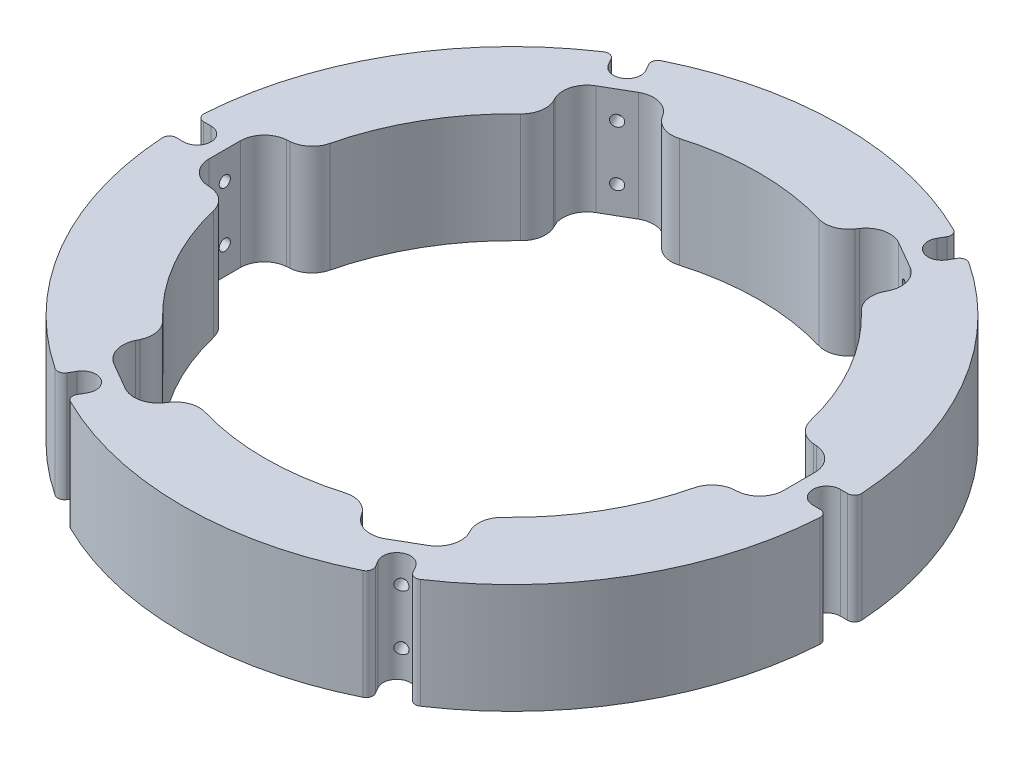
SolidWorks part; units mm, degrees
material "6061-T6 (SS)"
ref_plane "Front Plane" through (0, 0, 0) normal (0, 0, 1) x (1, 0, 0)
ref_plane "Top Plane" through (0, 0, 0) normal (0, 1, 0) x (1, 0, 0)
ref_plane "Right Plane" through (0, 0, 0) normal (1, 0, 0) x (0, 0, -1)
sketch "Sketch1" plane through (0, 0, 0) normal (0, 1, 0) x (1, 0, 0)
  circle A0 centre (0, 0) radius 76.2
  circle A1 centre (0, 0) radius 57.15
  dimension "D1" = 152.4
  dimension "D2" = 19.05
extrude "Boss-Extrude1" add sketch "Sketch1" against normal blind 12.7
sketch "Sketch3" plane through (0, -12.7, 0) normal (0, -1, 0) x (-1, 0, 0)
  line L0 (-76.1338, 3.175) -> (-72.771, 3.175)
  line L1 (-76.1338, -3.175) -> (-72.771, -3.175)
  circle A0 centre (0, 0) radius 76.2 construction
  arc A1 (-72.771, 3.175) -> (-72.771, -3.175) centre (-72.771, 0) cw
  arc A2 (-76.1338, -3.175) -> (-76.1338, 3.175) centre (0, 0) cw
  point P9 (-69.596, 0)
  point P13 (-76.2, 0)
  dimension "D1" = 6.35
  dimension "D2" = 6.604
extrude "Cut-Extrude1" cut sketch "Sketch3" against normal blind 12.7
sketch "Sketch4" plane through (0, -12.7, 0) normal (0, -1, 0) x (-1, 0, 0)
  line L0 (-66.421, 8.7312) -> (-66.421, -8.7312)
  line L1 (-66.421, -8.7312) -> (-56.3507, -9.525)
  line L2 (-56.3507, -9.525) -> (-56.3507, 9.525)
  line L3 (-56.3507, 9.525) -> (-66.421, 8.7312)
  line L4 (-66.421, 0) -> (0, 0) construction
  circle A0 centre (0, 0) radius 57.15 construction
  dimension "D1" = 3.175
  dimension "D2" = 19.05
  dimension "D3" = 17.4625
extrude "Cut-Extrude2" cut sketch "Sketch4" against normal through all
hole_wizard "#5-40 Tapped Hole1" positions "Sketch5" profile "Sketch6" tap size "#5-40" standard "ANSI Inch" end condition through all
sketch "Sketch5" plane through (66.421, 0, 0) normal (-1, 0, 0) x (0, 0, 1)
  line L0 (-8.7312, -12.7) -> (8.7312, -12.7) construction
  point P0 (0, -6.35)
  dimension "D1" = 6.35
sketch "Sketch6" plane through (66.421, -6.35, 0) normal (0, 1, 0) x (0, 0, 1)
  line L0 (0, 0) -> (0, 9.7128)
  line L1 (0, 9.7128) -> (1.289, 9.7128)
  line L2 (1.289, 9.7128) -> (1.289, 0)
  line L5 (1.289, 0) -> (0, 0)
  line L11 (0, -6.35) -> (0, 107.95) construction
  dimension "Thru Tap Drill Dia." = 2.5781
  dimension "Thru Tap Drill Depth" = 9.7128
cosmetic thread "Hole Thread1" parameters "D2"=3.175
fillet "Fillet1" radius 1.5875 2 edges at (76.1338, -6.35, 3.175) (76.1338, -6.35, -3.175)
fillet "Fillet2" radius 5.5562 4 edges at (66.421, -6.35, 8.7312) (66.421, -6.35, -8.7312) (56.3507, -6.35, 9.525) (56.3507, -6.35, -9.525)
pattern_circular "CirPattern1" count 6 over 360 about axis through (0, -12.7, 0) along (0, 1, 0) of "Cut-Extrude1", "Cut-Extrude2", "Fillet2", "Fillet1", "#5-40 Tapped Hole1"
cosmetic thread "Hole Thread2" parameters "D2"=3.175
cosmetic thread "Hole Thread3" parameters "D2"=3.175
cosmetic thread "Hole Thread4" parameters "D2"=3.175
cosmetic thread "Hole Thread5" parameters "D2"=3.175
cosmetic thread "Hole Thread6" parameters "D2"=3.175
mirror "Mirror3" about plane through (0, 0, 0) normal (0, 1, 0) of bodies 103
cosmetic thread "Hole Thread8" parameters "D2"=3.175
cosmetic thread "Hole Thread9" parameters "D2"=3.175
cosmetic thread "Hole Thread10" parameters "D2"=3.175
cosmetic thread "Hole Thread11" parameters "D2"=3.175
cosmetic thread "Hole Thread12" parameters "D2"=3.175
cosmetic thread "Hole Thread13" parameters "D2"=3.175
